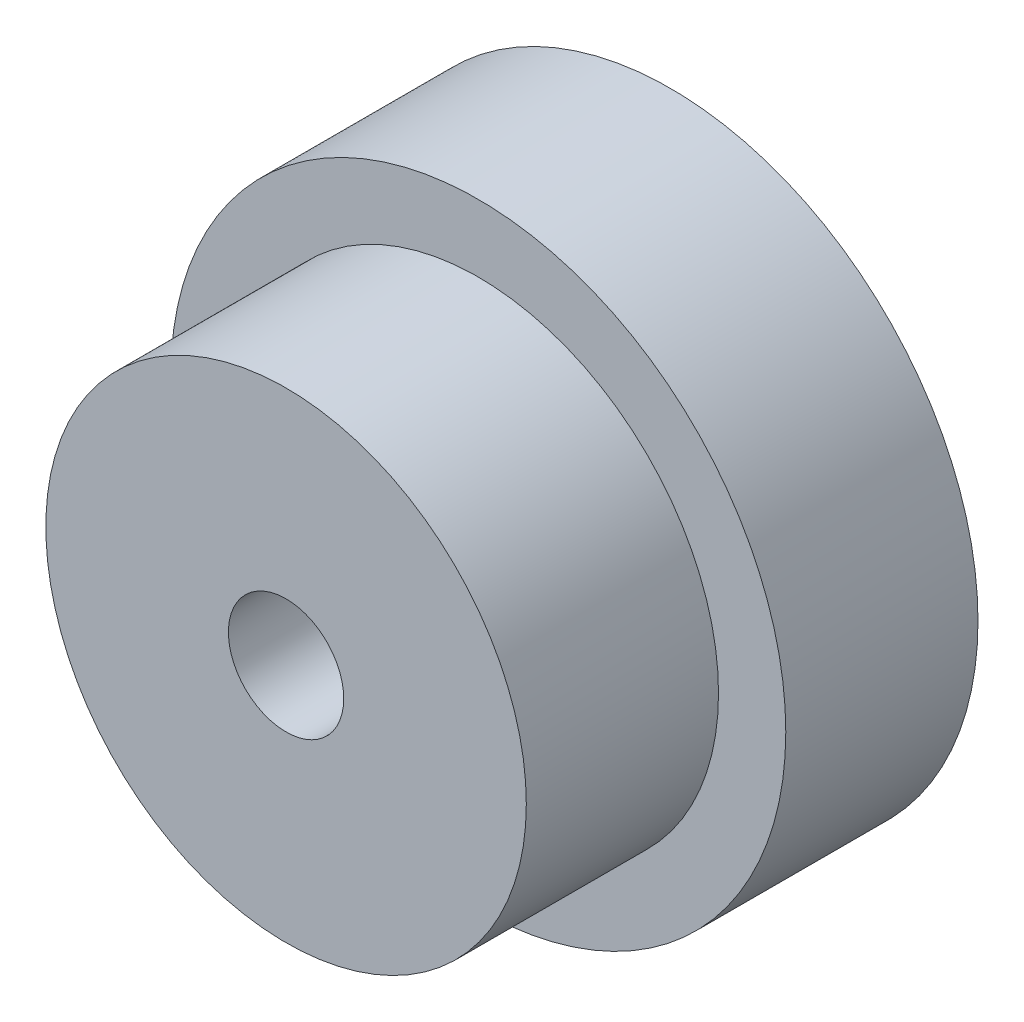
SolidWorks part; units mm, degrees
material "Commercial Bronze, UNS C22000 (90-10 Bronze)"
ref_plane "Front Plane" through (0, 0, 0) normal (0, 0, 1) x (1, 0, 0)
ref_plane "Top Plane" through (0, 0, 0) normal (0, 1, 0) x (1, 0, 0)
ref_plane "Right Plane" through (0, 0, 0) normal (1, 0, 0) x (0, 0, -1)
sketch "Sketch1" plane through (0, 0, 0) normal (0, 0, 1) x (1, 0, 0)
  circle A0 centre (0, 0) radius 3
  circle A1 centre (0, 0) radius 16
  circle A2 centre (0, 0) radius 12.5
  dimension "D1" = 32
  dimension "D2" = 6
  dimension "D3" = 25
extrude "Boss-Extrude1" add sketch "Sketch1" along normal blind 10 contours A1 A2 | A2 A0 region at (-15.5475, 0, 0) region at (-12.1464, 0, 0)
extrude "Boss-Extrude2" add sketch "Sketch1<3>" along normal blind 20 contours A2 A0 region at (-12.1464, 0, 0)
sketch "Sketch1<3>" plane through (0, 0, 0) normal (0, 0, 1) x (1, 0, 0) same geometry as "Sketch1"
